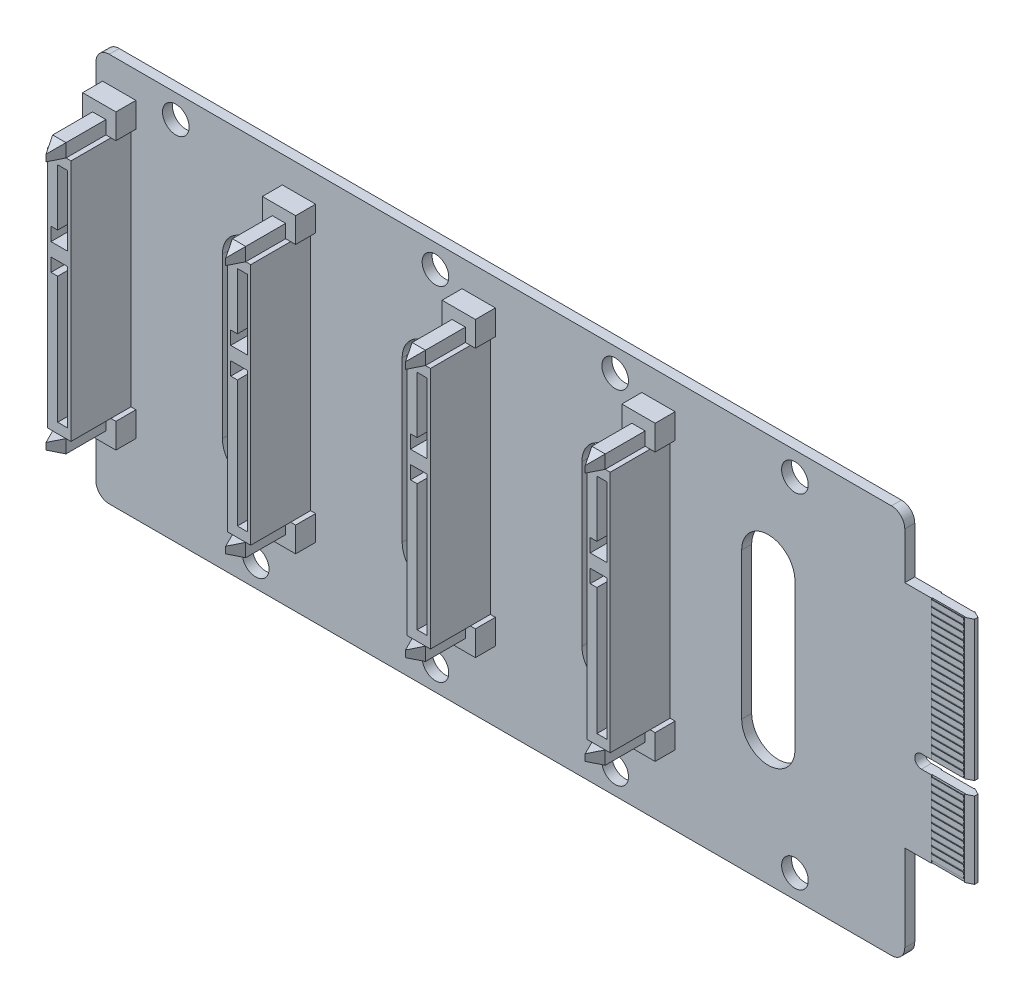
SolidWorks part; units mm, degrees
ref_plane "前视基准面" through (0, 0, 0) normal (0, 0, 1) x (1, 0, 0)
ref_plane "上视基准面" through (0, 0, 0) normal (0, 1, 0) x (1, 0, 0)
ref_plane "右视基准面" through (0, 0, 0) normal (1, 0, 0) x (0, 0, -1)
sketch "草图1" plane through (0, 0, 0) normal (0, 0, 1) x (1, 0, 0)
  line L1 (65.75, 29.25) -> (-65.75, 29.25)
  line L2 (65.75, 29.25) -> (65.75, -29.25)
  line L3 (65.75, -29.25) -> (-65.75, -29.25)
  line L4 (-65.75, 29.25) -> (-65.75, -29.25)
  line L5 (65.75, 29.25) -> (-65.75, -29.25) construction
  line L6 (65.75, -29.25) -> (-65.75, 29.25) construction
  point P0 (0, 0)
  dimension "D1" = 131.5
  dimension "D2" = 58.5
extrude "凸台-拉伸1" add sketch "草图1" along normal blind 1.5
chamfer "倒角1" distance 0.5 distance2 1 1 edges at (65.75, 0, 1.5) first distance on face at (65.75, 0, 0.75)
chamfer "倒角2" distance 1 distance2 0.5 1 edges at (65.75, 0, 0) first distance on face at (0, 0, 0)
sketch "草图2" plane through (0, 0, 0) normal (0, 0, 1) x (1, 0, 0)
  line L0 (65.75, -29.25) -> (65.75, 29.25) construction
  line L1 (65.75, 29.25) -> (55.75, 29.25)
  line L2 (65.75, 29.25) -> (65.75, 20.25)
  line L3 (65.75, 20.25) -> (55.75, 20.25)
  line L4 (55.75, 29.25) -> (55.75, 20.25)
  line L5 (65.75, -29.25) -> (55.75, -29.25)
  line L6 (65.75, -29.25) -> (65.75, -14.25)
  line L7 (65.75, -14.25) -> (55.75, -14.25)
  line L8 (55.75, -29.25) -> (55.75, -14.25)
  line L9 (65.75, -0.75) -> (58.25, -0.75)
  line L10 (65.75, -0.75) -> (65.75, -2.75)
  line L11 (65.75, -2.75) -> (58.25, -2.75)
  line L13 (65.75, 29.25) -> (65.75, -29.25) construction
  line L14 (64.75, 29.25) -> (-65.75, 29.25) construction
  line L15 (-65.75, -29.25) -> (64.75, -29.25) construction
  arc A0 (58.25, -0.75) -> (58.25, -2.75) centre (58.25, -1.75) ccw
  point P17 (57.25, -1.75)
  dimension "D1" = 34.5
  dimension "D2" = 15
  dimension "D3" = 10
  dimension "D4" = 2
  dimension "D5" = 11.5
  dimension "D6" = 8.5
extrude "切除-拉伸1" cut sketch "草图2" along normal through all
sketch "草图3" plane through (0, 0, 1.5) normal (0, 0, 1) x (1, 0, 0)
  line L0 (55.75, -14.25) -> (55.75, -29.25) construction
  line L1 (-65.75, -29.25) -> (55.75, -29.25) construction
  circle A0 centre (39.25, -25.75) radius 2
  dimension "D3" = 4
  dimension "D1" = 16.5
  dimension "D2" = 3.5
extrude "切除-拉伸3" cut sketch "草图3" against normal through all
pattern_linear "阵列(线性)1" count 4 spacing 27 along (-1, 0, 0) of "切除-拉伸3"
sketch "草图4" plane through (0, 0, 0) normal (0, 0, 1) x (1, 0, 0)
  line L0 (39.25, -25.75) -> (39.25, -16.1868) construction
  line L2 (0, 0) -> (85.6567, 0) construction
  circle A0 centre (39.25, 25.75) radius 2
  circle A1 centre (39.25, -25.75) radius 2 construction
extrude "切除-拉伸4" cut sketch "草图4" along normal through all
pattern_linear "阵列(线性)2" count 3 spacing 27 along (-1, 0, 0) count 2 spacing 93 along (-1, 0, 0) of "切除-拉伸4" pattern seed only yes
sketch "草图5" plane through (0, 0, 0) normal (0, 0, 1) x (1, 0, 0)
  line L0 (-42.75, 11.75) -> (-42.75, -12.25) construction
  line L1 (-38.75, 11.75) -> (-38.75, -12.25)
  line L2 (-46.75, 11.75) -> (-46.75, -12.25)
  line L3 (-65.75, -29.25) -> (55.75, -29.25) construction
  line L5 (55.75, 29.25) -> (-65.75, 29.25) construction
  line L6 (-65.75, 29.25) -> (-65.75, -29.25) construction
  arc A0 (-38.75, 11.75) -> (-46.75, 11.75) centre (-42.75, 11.75) ccw
  arc A1 (-46.75, -12.25) -> (-38.75, -12.25) centre (-42.75, -12.25) ccw
  point P2 (-42.75, -0.25)
  point P7 (-42.75, -16.25)
  point P10 (-42.75, 15.75)
  dimension "D1" = 13
  dimension "D2" = 13.5
  dimension "D3" = 8
  dimension "D4" = 19
extrude "切除-拉伸6" cut sketch "草图5" along normal through all
pattern_linear "阵列(线性)3" count 3 spacing 27 along (1, 0, 0) of "切除-拉伸6"
sketch "草图7" plane through (0, 0, 0) normal (0, 0, 1) x (1, 0, 0)
  line L0 (35.25, 12.25) -> (35.25, -9.75) construction
  line L1 (39.25, 12.25) -> (39.25, -9.75)
  line L2 (31.25, 12.25) -> (31.25, -9.75)
  line L3 (15.25, -12.25) -> (15.25, 11.75) construction
  line L4 (-65.75, -29.25) -> (55.75, -29.25) construction
  arc A0 (39.25, 12.25) -> (31.25, 12.25) centre (35.25, 12.25) ccw
  arc A1 (31.25, -9.75) -> (39.25, -9.75) centre (35.25, -9.75) ccw
  point P2 (35.25, 1.25)
  point P9 (35.25, -13.75)
  dimension "D1" = 8
  dimension "D2" = 16
  dimension "D3" = 15.5
  dimension "D4" = 22
extrude "切除-拉伸7" cut sketch "草图7" along normal through all
sketch "草图8" plane through (0, 0, 1.5) normal (0, 0, 1) x (1, 0, 0)
  line L0 (55.75, 29.25) -> (-65.75, 29.25) construction
  line L1 (-64.75, 25.25) -> (-59.75, 25.25)
  line L2 (-64.75, 25.25) -> (-64.75, -18.75)
  line L3 (-64.75, -18.75) -> (-59.75, -18.75)
  line L4 (-59.75, 25.25) -> (-59.75, -18.75)
  line L5 (-64.75, 25.25) -> (-59.75, -18.75) construction
  line L6 (-64.75, -18.75) -> (-59.75, 25.25) construction
  line L7 (-65.75, 29.25) -> (-65.75, -29.25) construction
  point P0 (-62.25, 3.25)
  dimension "D1" = 4
  dimension "D2" = 1
  dimension "D3" = 44
  dimension "D4" = 5
extrude "凸台-拉伸2" add sketch "草图8" along normal blind 11
sketch "草图9" plane through (0, 0, 12.5) normal (0, 0, 1) x (1, 0, 0)
  line L0 (-64.75, 25.25) -> (-64.75, -18.75) construction
  line L1 (-64.75, 21.5) -> (-59.75, 21.5)
  line L2 (-64.75, 21.5) -> (-64.75, -15)
  line L3 (-64.75, -15) -> (-59.75, -15)
  line L4 (-59.75, 21.5) -> (-59.75, -15)
  line L5 (-59.75, -18.75) -> (-59.75, 25.25) construction
  line L7 (-59.75, 3.25) -> (-46.5907, 3.25) construction
  line L8 (-59.75, -18.75) -> (-59.75, 25.25) construction
  line L9 (-59.75, 25.25) -> (-64.75, 25.25) construction
  line L10 (-64.75, -18.75) -> (-59.75, -18.75) construction
  dimension "D2" = 36.5
extrude "切除-拉伸8" cut sketch "草图9" against normal blind 2
sketch "草图10" plane through (0, 0, 10.5) normal (0, 0, 1) x (1, 0, 0)
  line L0 (-59.75, 21.5) -> (-64.75, 21.5) construction
  line L5 (-64.75, -15) -> (-59.75, -15) construction
  line L6 (-62.25, 25.25) -> (-62.25, 33.4688) construction
  line L7 (-59.75, 25.25) -> (-64.75, 25.25) construction
  line L8 (-64.75, -15) -> (-59.75, -15) construction
  line L9 (-60.5, 21.5) -> (-59.75, 21.5)
  line L10 (-60.5, 21.5) -> (-60.5, -15)
  line L11 (-60.5, -15) -> (-59.75, -15)
  line L12 (-59.75, 21.5) -> (-59.75, -15)
  line L13 (-64, -15) -> (-64.75, -15)
  line L14 (-64, -15) -> (-64, 21.5)
  line L15 (-64, 21.5) -> (-64.75, 21.5)
  line L16 (-64.75, -15) -> (-64.75, 21.5)
  dimension "D1" = 3.5
extrude "切除-拉伸9" cut sketch "草图10" against normal up to surface (9 mm away) up to face at (35.25, 1.25, 1.5)
sketch "草图11" plane through (0, 0, 10.5) normal (0, 0, 1) x (1, 0, 0)
  line L0 (-61, 20) -> (-61, 9.5)
  line L1 (-62.5, 20) -> (-61, 20)
  line L2 (-62.5, 20) -> (-62.5, 11.5)
  line L5 (-61, 9.5) -> (-63.5, 9.5)
  line L7 (-62.5, 11.5) -> (-63.5, 11.5)
  line L8 (-63.5, 9.5) -> (-63.5, 11.5)
  line L10 (-63.5, 7.5) -> (-63.5, 5.5)
  line L11 (-63.5, 5.5) -> (-62.5, 5.5)
  line L14 (-61, 7.5) -> (-61, -13.5)
  line L15 (-61, -13.5) -> (-62.5, -13.5)
  line L16 (-62.5, 5.5) -> (-62.5, -13.5)
  line L17 (-63.5, 7.5) -> (-61, 7.5)
  line L18 (-60.5, 21.5) -> (-60.5, -15) construction
  line L20 (-64, -15) -> (-64, 21.5) construction
  line L21 (-59.75, 21.5) -> (-64.75, 21.5) construction
  dimension "D1" = 0.5
  dimension "D2" = 1.5
  dimension "D3" = 0.5
  dimension "D4" = 21
  dimension "D5" = 10.5
  dimension "D6" = 1.5
  dimension "D7" = 2
  dimension "D8" = 2
  dimension "D9" = 2
extrude "切除-拉伸10" cut sketch "草图11" against normal blind 5
pattern_linear "阵列(线性)4" count 4 spacing 27 along (1, 0, 0) of "凸台-拉伸2", "切除-拉伸8", "切除-拉伸9", "切除-拉伸10"
sketch "草图12" plane through (0, 0, 12.5) normal (0, 0, 1) x (1, 0, 0)
  line L0 (-62.25, 25.25) -> (-62.25, 27.8468) construction
  line L1 (-59.75, 25.25) -> (-64.75, 25.25) construction
  line L2 (-63.25, -15) -> (-64.75, -15)
  line L3 (-63.25, 23.5) -> (-61.25, 23.5)
  line L4 (-63.25, 23.5) -> (-63.25, 21.5)
  line L6 (-61.25, 23.5) -> (-61.25, 21.5)
  line L7 (-63.25, 21.5) -> (-64.75, 21.5)
  line L8 (-64.75, 21.5) -> (-64.75, 25.25)
  line L9 (-64.75, 25.25) -> (-64.75, 21.5) construction
  line L10 (-59.75, 25.25) -> (-64.75, 25.25) construction
  line L11 (-64.75, 25.25) -> (-59.75, 25.25)
  line L12 (-59.75, 25.25) -> (-59.75, 21.5)
  line L13 (-59.75, 21.5) -> (-61.25, 21.5)
  line L14 (-64, -15) -> (-60.5, -15) construction
  line L16 (-63.25, -15) -> (-63.25, -17)
  line L17 (-63.25, -17) -> (-61.25, -17)
  line L18 (-61.25, -15) -> (-61.25, -17)
  line L19 (-64.75, -15) -> (-64.75, -18.75)
  line L20 (-64.75, -18.75) -> (-59.75, -18.75) construction
  line L21 (-64.75, -15) -> (-64.75, -18.75) construction
  line L22 (-64.75, -18.75) -> (-59.75, -18.75)
  line L23 (-59.75, -18.75) -> (-59.75, -15)
  line L24 (-59.75, -15) -> (-61.25, -15)
  dimension "D1" = 2
  dimension "D2" = 2
extrude "切除-拉伸11" cut sketch "草图12" against normal blind 8
chamfer "倒角3" distance 1 distance2 2 6 edges at (-61.25, 22.5, 12.5) (-62.25, 23.5, 12.5) (-63.25, 22.5, 12.5) (-61.25, -16, 12.5) (-62.25, -17, 12.5) (-63.25, -16, 12.5) first distance on face at (-62.25, 22.5, 12.5) first distance on face at (-62.25, -16, 12.5)
pattern_linear "阵列(线性)9" count 4 spacing 27 along (1, 0, 0) of "切除-拉伸11"
chamfer "倒角4" distance 1 distance2 2 18 edges at (19.75, -16, 12.5) (18.75, -17, 12.5) (17.75, -16, 12.5) (19.75, 22.5, 12.5) (18.75, 23.5, 12.5) (17.75, 22.5, 12.5) (-7.25, -16, 12.5) (-8.25, -17, 12.5) (-9.25, -16, 12.5) (-7.25, 22.5, 12.5) (-8.25, 23.5, 12.5) (-9.25, 22.5, 12.5) (-34.25, -16, 12.5) (-35.25, -17, 12.5) (-36.25, -16, 12.5) (-34.25, 22.5, 12.5) (-35.25, 23.5, 12.5) (-36.25, 22.5, 12.5) first distance on face at (18.75, -16, 12.5) first distance on face at (18.75, 22.5, 12.5) first distance on face at (-8.25, -16, 12.5) first distance on face at (-8.25, 22.5, 12.5) first distance on face at (-35.25, -16, 12.5) first distance on face at (-35.25, 22.5, 12.5)
sketch "草图13" plane through (0, 0, 1.5) normal (0, 0, 1) x (1, 0, 0)
  line L0 (64.75, -14.25) -> (55.75, -14.25) construction
  line L1 (64.75, 20.25) -> (59.75, 20.25)
  line L2 (64.75, 20.25) -> (64.75, -14.25)
  line L3 (64.75, -14.25) -> (59.75, -14.25)
  line L4 (59.75, 20.25) -> (59.75, -14.25)
  dimension "D1" = 5
extrude "切除-拉伸12" cut sketch "草图13" against normal blind 0.1
ref_plane "基准面1" through (0, 0, 0.75) normal (0, 0, 1) x (1, 0, 0)
sketch "草图14" plane through (0, 0, 1.4) normal (0, 0, 1) x (1, 0, 0)
  line L0 (59.75, 20.25) -> (59.75, -0.75) construction
  line L1 (64.75, -0.75) -> (64.75, 20.25) construction
  line L2 (59.75, 20.05) -> (64.55, 20.05)
  line L3 (59.75, 20.05) -> (59.75, 19.25)
  line L4 (59.75, 19.25) -> (64.55, 19.25)
  line L5 (64.55, 20.05) -> (64.55, 19.75)
  line L6 (64.55, 19.75) -> (64.75, 19.75)
  line L8 (64.55, 19.55) -> (64.75, 19.55)
  line L9 (64.75, 19.75) -> (64.75, 19.55)
  line L10 (64.55, 19.55) -> (64.55, 19.25)
  line L11 (64.75, 20.25) -> (59.75, 20.25) construction
  line L12 (59.75, 19.65) -> (60.1834, 19.65) construction
  dimension "D1" = 0.2
  dimension "D2" = 0.2
  dimension "D3" = 0.2
  dimension "D4" = 0.8
extrude "凸台-拉伸3" add sketch "草图14" along normal blind 0.09
pattern_linear "阵列(线性)11" count 21 spacing 1 along (0, -1, 0) of "凸台-拉伸3"
sketch "草图15" plane through (0, 0, 1.4) normal (0, 0, 1) x (1, 0, 0)
  line L0 (64.75, -14.25) -> (64.75, -2.75) construction
  line L1 (59.75, -3.05) -> (64.55, -3.05)
  line L2 (59.75, -3.05) -> (59.75, -3.85)
  line L3 (59.75, -3.85) -> (64.55, -3.85)
  line L4 (64.55, -3.05) -> (64.55, -3.35)
  line L5 (64.55, -3.35) -> (64.75, -3.35)
  line L7 (64.55, -3.55) -> (64.75, -3.55)
  line L8 (64.75, -3.35) -> (64.75, -3.55)
  line L9 (64.55, -3.55) -> (64.55, -3.85)
  line L10 (59.75, -3.45) -> (60.5534, -3.45) construction
  line L11 (64.75, -2.75) -> (59.75, -2.75) construction
  line L12 (59.75, -2.75) -> (59.75, -14.25) construction
  dimension "D1" = 0.8
  dimension "D2" = 0.2
  dimension "D3" = 0.2
  dimension "D4" = 0.3
extrude "凸台-拉伸4" add sketch "草图15" along normal blind 0.09
pattern_linear "阵列(线性)12" count 11 spacing 1 along (0, -1, 0) of "凸台-拉伸4"
mirror "镜向1" about plane through (0, 0, 0.75) normal (0, 0, 1) of "切除-拉伸12", "阵列(线性)12", "凸台-拉伸4", "阵列(线性)11", "凸台-拉伸3"
fillet "圆角1" radius 2 4 edges at (-65.75, 29.25, 0.75) (-65.75, -29.25, 0.75) (55.75, -29.25, 0.75) (55.75, 29.25, 0.75)
